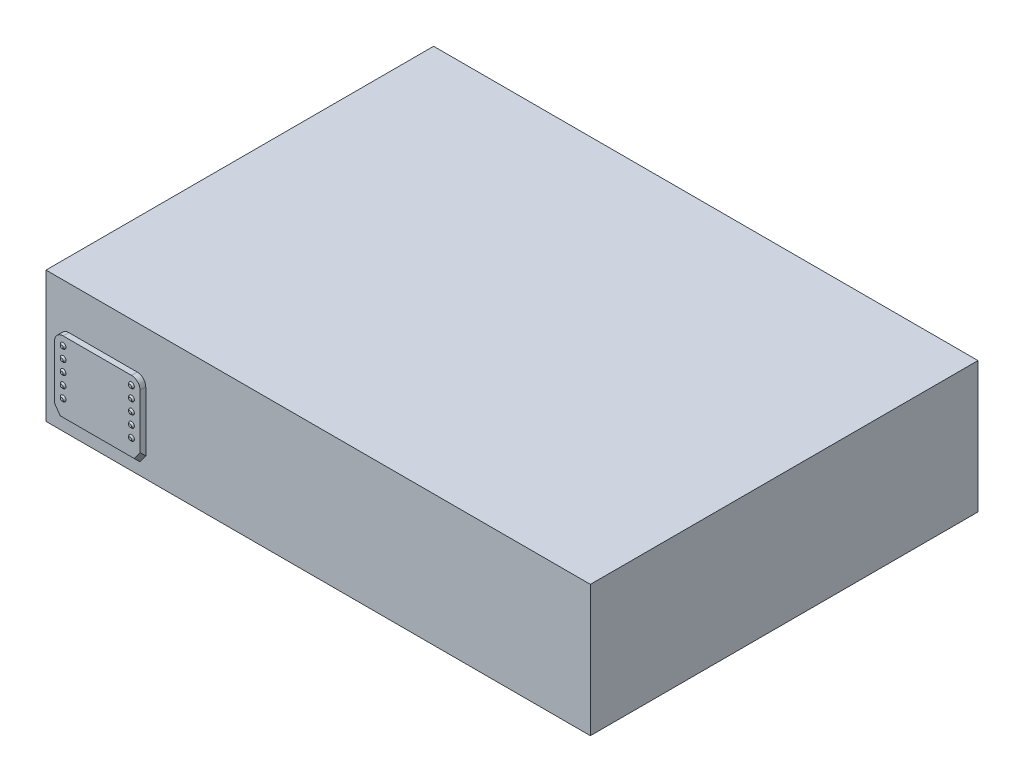
SolidWorks part; units mm, degrees
ref_plane "Front Plane" through (0, 0, 0) normal (0, 0, 1) x (1, 0, 0)
ref_plane "Top Plane" through (0, 0, 0) normal (0, 1, 0) x (1, 0, 0)
ref_plane "Right Plane" through (0, 0, 0) normal (1, 0, 0) x (0, 0, -1)
sketch "Sketch1" plane through (0, 0, 0) normal (0, 1, 0) x (1, 0, 0)
  line L1 (0, 0) -> (191, 0)
  line L2 (0, 0) -> (0, 136)
  line L3 (0, 136) -> (191, 136)
  line L4 (191, 0) -> (191, 136)
  dimension "D1" = 191
  dimension "D2" = 136
extrude "Boss-Extrude1" add sketch "Sketch1" along normal blind 46
sketch "Sketch3" plane through (0, 0, 0) normal (0, -1, 0) x (1, 0, 0)
  line L0 (0, -136) -> (0, 0) construction
  line L1 (5, -5) -> (186, -5)
  line L2 (5, -5) -> (5, -131)
  line L3 (5, -131) -> (186, -131)
  line L4 (186, -5) -> (186, -131)
  line L6 (191, -136) -> (0, -136) construction
  line L7 (191, 0) -> (191, -136) construction
  line L8 (0, 0) -> (191, 0) construction
  dimension "D1" = 5
  dimension "D2" = 5
  dimension "D3" = 5
  dimension "D4" = 5
extrude "Cut-Extrude1" cut sketch "Sketch3" against normal offset from surface (41 mm away) 5 contours L2 L3 L4 L1 up to face at (95.5, 46, -68)
ref_point "FrontLeft"
sketch "Sketch5" plane through (0, 0, -136) normal (0, 0, -1) x (-1, 0, 0)
  line L0 (-191, 46) -> (-119.5, 46)
  line L1 (-191, 46) -> (0, 46) construction
  line L2 (-119.5, 46) -> (-119.5, 0) construction
  line L3 (-191, 0) -> (0, 0) construction
  point P5 (-119.5, 23)
  dimension "D1" = 71.5
sketch "Sketch8" plane through (0, 0, 0) normal (0, 0, 1) x (1, 0, 0)
  line L1 (119.5, 46) -> (119.5, 0) construction
  line L2 (0, 46) -> (191, 46) construction
  line L3 (0, 0) -> (191, 0) construction
  point P0 (119.5, 23)
ref_point "SuspensionMountLeft"
ref_point "SuspensionMountRight"
sketch "Sketch9" plane through (0, 0, -136) normal (0, 0, -1) x (-1, 0, 0)
  line L0 (0, 46) -> (0, 0) construction
  line L1 (-5, 31) -> (-35, 31)
  line L2 (-5, 31) -> (-5, 6.2153)
  line L3 (-5, 6.2153) -> (-35, 6.2153)
  line L4 (-35, 31) -> (-35, 6.2153)
  line L5 (-191, 46) -> (0, 46) construction
  dimension "D1" = 5
  dimension "D2" = 15
  dimension "D3" = 30
extrude "Boss-Extrude2" add sketch "Sketch9" along normal blind 2
chamfer "Chamfer2" distance 2 angle 45 1 edges at (20, 6.2153, -136)
fillet "Fillet1" radius 3 2 edges at (35, 31, -137) (5, 31, -137)
chamfer "Chamfer3" distance 2 angle 45 2 edges at (35, 5.2153, -137) (5, 5.2153, -137)
sketch "Sketch10" plane through (0, 0, 0) normal (0, 0, 1) x (1, 0, 0)
  line L4 (35, 31) -> (5, 31)
  line L5 (35, 6.2153) -> (35, 31)
  line L6 (5, 6.2153) -> (35, 6.2153)
  line L7 (5, 31) -> (5, 6.2153)
  line L8 (35, 31) -> (5, 31)
  line L9 (35, 6.2153) -> (35, 31)
  line L10 (5, 6.2153) -> (35, 6.2153)
  line L11 (5, 31) -> (5, 6.2153)
  dimension "D1" = 0
extrude "Boss-Extrude3" add sketch "Sketch10" along normal blind 2
chamfer "Chamfer4" distance 2 angle 45 1 edges at (20, 6.2153, 0)
fillet "Fillet2" radius 3 2 edges at (5, 31, 1) (35, 31, 1)
chamfer "Chamfer5" distance 2 angle 45 2 edges at (35, 5.2153, 1) (5, 5.2153, 1)
sketch "Sketch11" plane through (0, 0, 2) normal (0, 0, 1) x (1, 0, 0)
  line L0 (8, 28) -> (8, 6.2153) construction
  line L1 (7, 6.2153) -> (33, 6.2153) construction
  line L2 (32, 28) -> (32, 6.2153) construction
  circle A0 centre (8, 28) radius 1
  circle A1 centre (8, 24) radius 1
  circle A2 centre (8, 20) radius 1
  circle A3 centre (8, 16) radius 1
  circle A4 centre (8, 12) radius 1
  circle A5 centre (32, 28) radius 1
  circle A6 centre (32, 24) radius 1
  circle A7 centre (32, 20) radius 1
  circle A8 centre (32, 16) radius 1
  circle A9 centre (32, 12) radius 1
  dimension "D1" = 2
  dimension "D3" = 2
  dimension "D2" = 5
  dimension "D4" = 5
extrude "Boss-Extrude4" add sketch "Sketch11" along normal blind 0.5
chamfer "Chamfer6" distance 0.5 angle 45 10 edges at (33, 12, 2.5) (33, 16, 2.5) (33, 28, 2.5) (33, 24, 2.5) (33, 20, 2.5) (9, 12, 2.5) (9, 16, 2.5) (9, 20, 2.5) (9, 24, 2.5) (9, 28, 2.5)
sketch "Sketch12" plane through (0, 0, -138) normal (0, 0, -1) x (-1, 0, 0)
  circle A1 centre (-32, 28) radius 1
  circle A2 centre (-32, 28) radius 1
  circle A3 centre (-8, 20) radius 1
  circle A4 centre (-8, 20) radius 1
  circle A5 centre (-8, 24) radius 1
  circle A6 centre (-8, 24) radius 1
  circle A7 centre (-8, 28) radius 1
  circle A8 centre (-8, 28) radius 1
  circle A9 centre (-32, 12) radius 1
  circle A10 centre (-32, 12) radius 1
  circle A11 centre (-32, 16) radius 1
  circle A12 centre (-32, 16) radius 1
  circle A13 centre (-32, 20) radius 1
  circle A14 centre (-32, 20) radius 1
  circle A15 centre (-32, 24) radius 1
  circle A16 centre (-32, 24) radius 1
  circle A17 centre (-8, 12) radius 1
  circle A18 centre (-8, 12) radius 1
  circle A19 centre (-8, 16) radius 1
  circle A20 centre (-8, 16) radius 1
  dimension "D1" = 0
  dimension "D2" = 0
  dimension "D3" = 0
  dimension "D4" = 0
  dimension "D5" = 0
  dimension "D6" = 0
  dimension "D7" = 0
  dimension "D8" = 0
  dimension "D9" = 0
  dimension "D10" = 0
extrude "Boss-Extrude5" add sketch "Sketch12" along normal blind 0.5
chamfer "Chamfer8" distance 0.5 angle 45 10 edges at (7, 24, -138.5) (7, 28, -138.5) (31, 12, -138.5) (31, 16, -138.5) (31, 20, -138.5) (31, 24, -138.5) (31, 28, -138.5) (7, 12, -138.5) (7, 16, -138.5) (7, 20, -138.5)
